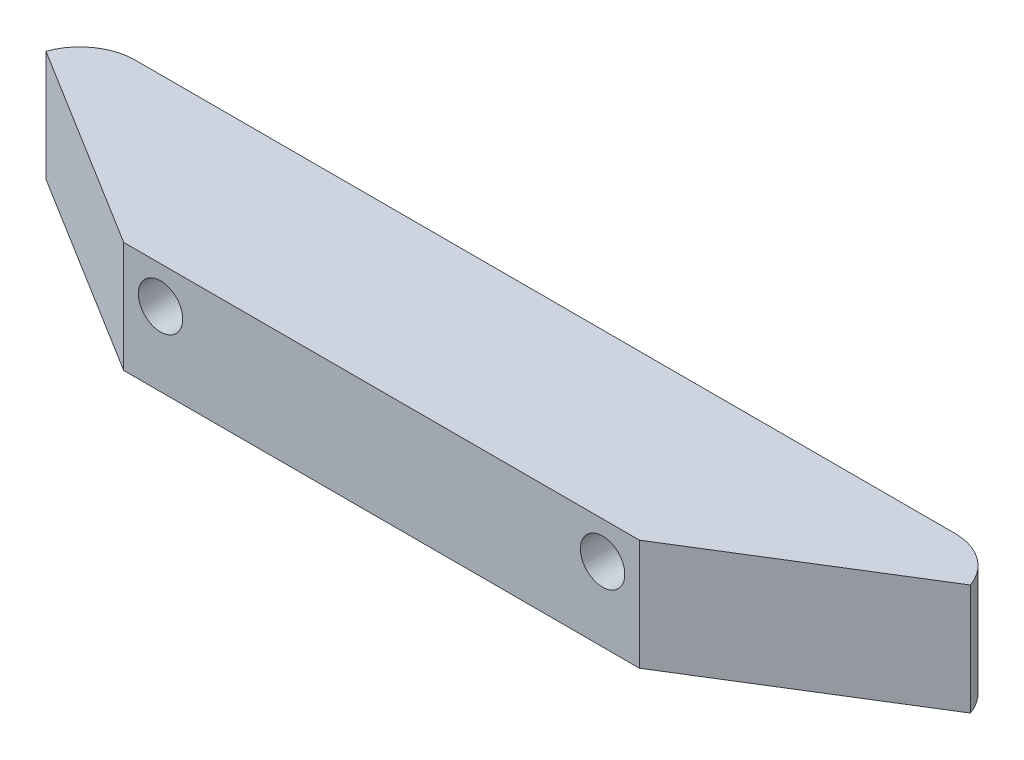
SolidWorks part; units mm, degrees
ref_plane "Front Plane" through (0, 0, 0) normal (0, 0, 1) x (1, 0, 0)
ref_plane "Top Plane" through (0, 0, 0) normal (0, 1, 0) x (1, 0, 0)
ref_plane "Right Plane" through (0, 0, 0) normal (1, 0, 0) x (0, 0, -1)
sketch "Sketch1" plane through (0, 0, 0) normal (0, 1, 0) x (1, 0, 0)
  line L0 (-50, 17.7) -> (50, 17.7)
  line L1 (-27.895, 0) -> (27.895, 0)
  line L2 (-50, 17.7) -> (-50, 13.7)
  line L3 (-50, 13.7) -> (-27.895, 0)
  line L4 (27.895, 0) -> (50, 13.7)
  line L5 (50, 13.7) -> (50, 17.7)
  point P5 (45.2034, 13.5182)
  point P9 (51.2528, 13.7)
  dimension "D1" = 17.7
  dimension "D2" = 4
  dimension "D3" = 55.79
  dimension "D4" = 100
extrude "Boss-Extrude1" add sketch "Sketch1" along normal blind 12
sketch "Sketch3" plane through (0, 0, 0) normal (0, 0, 1) x (1, 0, 0)
  line L0 (0, -55) -> (0, 55) construction
  line L1 (-27.895, 12) -> (27.895, 12) construction
  circle A0 centre (-23.91, 8) radius 2.4
  circle A1 centre (23.91, 8) radius 2.4
  dimension "D1" = 4.8
  dimension "D2" = 4
  dimension "D3" = 47.82
extrude "Cut-Extrude1" cut sketch "Sketch3" against normal blind 8.5
fillet "Fillet1" radius 6 2 edges at (50, 6, -17.7) (-50, 6, -17.7)
